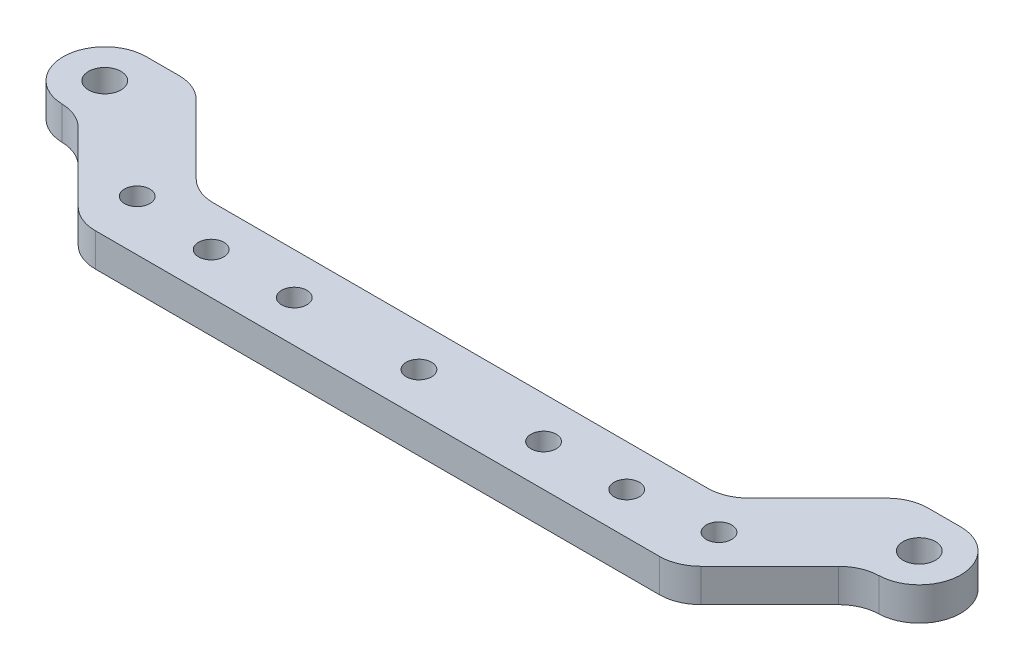
SolidWorks part; units mm, degrees
ref_plane "Front Plane" through (0, 0, 0) normal (0, 0, 1) x (1, 0, 0)
ref_plane "Top Plane" through (0, 0, 0) normal (0, 1, 0) x (1, 0, 0)
ref_plane "Right Plane" through (0, 0, 0) normal (1, 0, 0) x (0, 0, -1)
sketch "Sketch1" plane through (0, 0, 0) normal (0, 1, 0) x (1, 0, 0)
  line L0 (-44.6, -5) -> (-54.1, -5)
  line L1 (24.9, -16.2) -> (-35.1, -16.2)
  line L2 (24.9, -16.2) -> (24.9, -6.2)
  line L3 (24.9, -6.2) -> (-35.1, -6.2)
  line L4 (-35.1, -16.2) -> (-35.1, -6.2)
  line L5 (-35.1, -11.2) -> (-5.1, -11.2) construction
  line L6 (24.9, -16.2) -> (34.4, -16.2)
  line L7 (24.9, -16.2) -> (24.9, 5)
  line L8 (24.9, 5) -> (34.4, 5)
  line L9 (34.4, -16.2) -> (34.4, 5)
  line L10 (34.4, 5) -> (43.9, 5)
  line L11 (34.4, 5) -> (34.4, -5)
  line L12 (34.4, -5) -> (43.9, -5)
  line L13 (43.9, 5) -> (43.9, -5)
  line L14 (-5.1, -6.2) -> (-5.1, -16.2) construction
  line L15 (-5.1, -11.2) -> (24.9, -11.2) construction
  line L16 (15.65, -6.2) -> (-15.65, -6.2) construction
  line L17 (34.4, -16.2) -> (43.9, -16.2)
  line L18 (34.4, -16.2) -> (34.4, -5)
  line L19 (34.4, -5) -> (43.9, -5)
  line L20 (43.9, -16.2) -> (43.9, -5)
  line L21 (-54.1, 5) -> (-54.1, -5)
  line L22 (-44.6, 5) -> (-54.1, 5)
  line L23 (-44.6, 5) -> (-44.6, -5)
  line L24 (-44.6, -5) -> (-54.1, -5)
  line L25 (-54.1, -16.2) -> (-54.1, -5)
  line L26 (-44.6, -16.2) -> (-54.1, -16.2)
  line L27 (-44.6, -16.2) -> (-44.6, -5)
  line L28 (-35.1, 5) -> (-44.6, 5)
  line L29 (-44.6, -16.2) -> (-44.6, 5)
  line L30 (-35.1, -16.2) -> (-44.6, -16.2)
  line L31 (-35.1, -16.2) -> (-35.1, 5)
  circle A0 centre (43.9, 0) radius 1.9 construction
  circle A1 centre (43.9, 0) radius 1.9 construction
  circle A2 centre (43.9, 0) radius 1.95
  circle A3 centre (43.9, 0) radius 5
  circle A6 centre (-54.1, 0) radius 1.95
  circle A7 centre (-54.1, 0) radius 5
  circle A8 centre (-54.1, 0) radius 1.9 construction
  dimension "D1" = 3.9
  dimension "D2" = 10
  dimension "D5" = 9.5
  dimension "D6" = 10
extrude "Boss-Extrude1" add sketch "Sketch1" along normal blind 4 from surface at 6.3
chamfer "Chamfer1" distance 13 angle 45 2 edges at (24.9, 8.3, -5) (-35.1, 8.3, -5)
chamfer "Chamfer2" distance 13 angle 45 2 edges at (43.9, 8.3, 16.2) (-54.1, 8.3, 16.2)
fillet "Fillet1" radius 5 8 edges at (-48.1, 8.3, -5) (-36.9, 8.3, 6.2) (26.7, 8.3, 6.2) (37.9, 8.3, -5) (42.3472, 8.3, 4.7528) (30.9, 8.3, 16.2) (-41.1, 8.3, 16.2) (-52.5472, 8.3, 4.7528)
sketch "Sketch2" plane through (0, 10.3, 0) normal (0, 1, 0) x (1, 0, 0)
  line L0 (-5.1, -6.2) -> (-5.1, -16.2) construction
  line L1 (28.8289, -16.2) -> (-39.0289, -16.2) construction
  line L2 (29.9, -3) -> (29.9, -17.2) construction
  line L3 (24.9, -16.2) -> (-35.1, -16.2) construction
  line L4 (24.9, -16.2) -> (24.9, -6.2) construction
  line L5 (24.9, -6.2) -> (-35.1, -6.2) construction
  line L6 (-35.1, -16.2) -> (-35.1, -6.2) construction
  line L7 (24.9, -16.2) -> (-35.1, -6.2) construction
  line L8 (24.9, -6.2) -> (-35.1, -16.2) construction
  line L9 (24.6289, -6.2) -> (-34.8289, -6.2) construction
  line L11 (24.9, -16.2) -> (34.9, -16.2) construction
  line L12 (24.9, -16.2) -> (24.9, 13.8) construction
  line L13 (24.9, 13.8) -> (34.9, 13.8) construction
  line L14 (34.9, -16.2) -> (34.9, 13.8) construction
  line L16 (32.3645, -14.7355) -> (40.6393, -6.4607) construction
  line L17 (36.4355, 3.5355) -> (28.1645, -4.7355) construction
  line L18 (32.3645, -14.7355) -> (40.6393, -6.4607) construction
  line L19 (36.4355, 3.5355) -> (28.1645, -4.7355) construction
  line L20 (-5.1, -11.2) -> (24.9, -11.2) construction
  line L21 (9.9, -11.2) -> (9.9, -6.2) construction
  circle A0 centre (29.9, -10.1) radius 1.525
  circle A1 centre (-5.1, -11.2) radius 1.525
  circle A2 centre (9.9, -11.2) radius 1.525
  circle A3 centre (-40.1, -10.1) radius 1.525
  circle A4 centre (-20.1, -11.2) radius 1.525
  circle A5 centre (19.9, -11.2) radius 1.525
  circle A6 centre (-30.1, -11.2) radius 1.525
  point P5 (-5.1, -11.2)
  point P21 (29.9, 13.8)
  dimension "D4" = 3.05
  dimension "D5" = 5
  dimension "D1" = 60
  dimension "D2" = 10
  dimension "D3" = 30
extrude "Cut-Extrude1" cut sketch "Sketch2" against normal through all
